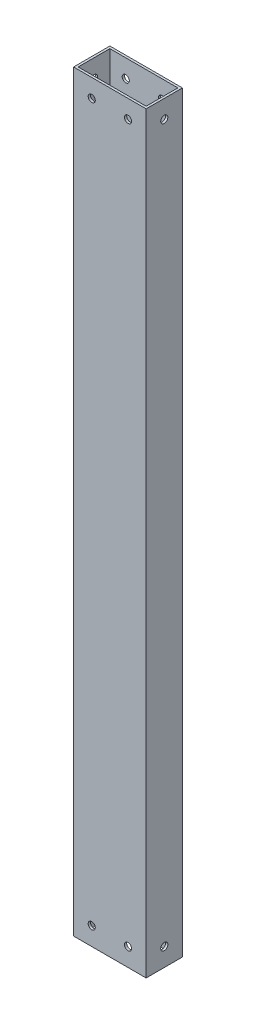
SolidWorks part; units mm, degrees
ref_plane "Front Plane" through (0, 0, 0) normal (0, 0, 1) x (1, 0, 0)
ref_plane "Top Plane" through (0, 0, 0) normal (0, 1, 0) x (1, 0, 0)
ref_plane "Right Plane" through (0, 0, 0) normal (1, 0, 0) x (0, 0, -1)
sketch "Sketch1" plane through (0, 0, 0) normal (0, 0, 1) x (1, 0, 0)
  line L1 (-25.4, -263.525) -> (25.4, -263.525)
  line L2 (-25.4, -263.525) -> (-25.4, 263.525)
  line L3 (-25.4, 263.525) -> (25.4, 263.525)
  line L4 (25.4, -263.525) -> (25.4, 263.525)
  line L5 (-25.4, -263.525) -> (25.4, 263.525) construction
  line L6 (-25.4, 263.525) -> (25.4, -263.525) construction
  point P0 (0, 0)
  dimension "D1" = 50.8
  dimension "D2" = 527.05
extrude "Boss-Extrude1" add sketch "Sketch1" along normal mid plane 25.4
shell "Shell1" thickness 1.5875 removed face at (0, -263.525, 0) removed face at (0, 263.525, 0)
sketch "Sketch2" plane through (0, 0, 0) normal (0, 0, 1) x (1, 0, 0)
  line L0 (-25.4, 263.525) -> (-25.4, -263.525) construction
  line L1 (-25.4, -263.525) -> (25.4, -263.525) construction
  line L2 (-25.4, 0) -> (25.4, 0) construction
  line L3 (25.4, -263.525) -> (25.4, 263.525) construction
  circle A0 centre (-12.7, -250.825) radius 2.4892
  circle A1 centre (12.7, -250.825) radius 2.4892
  circle A2 centre (12.7, 250.825) radius 2.4892
  circle A3 centre (-12.7, 250.825) radius 2.4892
  dimension "D1" = 4.9784
  dimension "D3" = 25.4
  dimension "D2" = 12.7
  dimension "D4" = 12.7
extrude "Cut-Extrude1" cut sketch "Sketch2" against normal through all both and the other way through all
sketch "Sketch3" plane through (0, 0, 0) normal (1, 0, 0) x (0, 0, -1)
  line L0 (-12.7, -263.525) -> (12.7, -263.525) construction
  line L1 (-12.7, 263.525) -> (12.7, 263.525) construction
  circle A0 centre (0, -250.825) radius 2.4892
  circle A1 centre (0, 250.825) radius 2.4892
  point P6 (0, -263.525)
  point P9 (0, 263.525)
  point P10 (0, 0)
  dimension "D1" = 4.9784
  dimension "D2" = 12.7
  dimension "D3" = 12.7
extrude "Cut-Extrude2" cut sketch "Sketch3" against normal through all both and the other way through all
